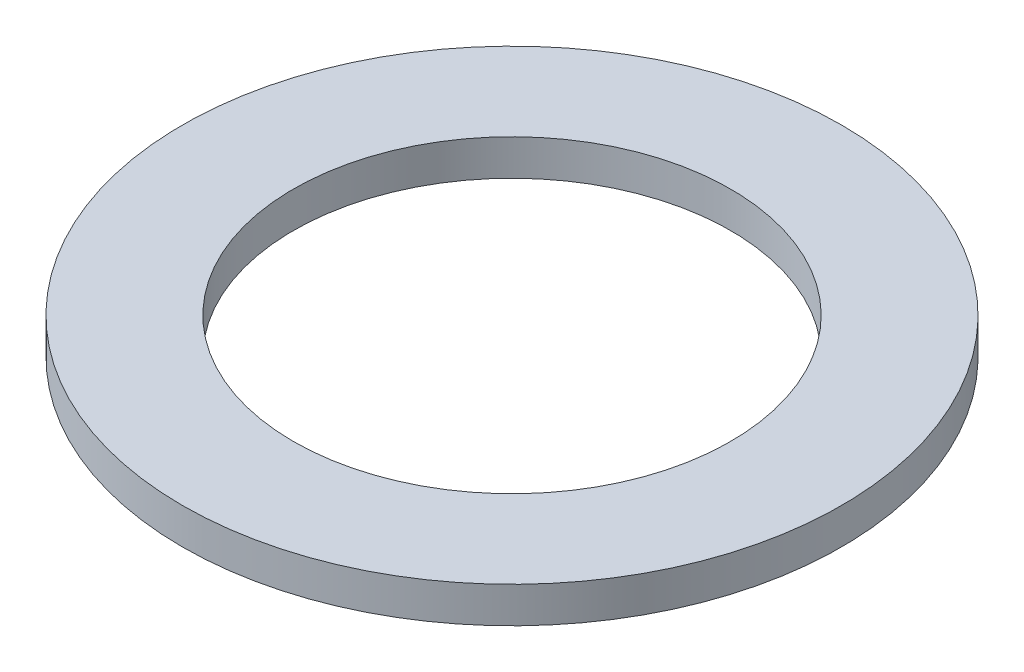
SolidWorks part; units mm, degrees
material "PET"
ref_plane "Front Plane" through (0, 0, 0) normal (0, 0, 1) x (1, 0, 0)
ref_plane "Top Plane" through (0, 0, 0) normal (0, 1, 0) x (1, 0, 0)
ref_plane "Right Plane" through (0, 0, 0) normal (1, 0, 0) x (0, 0, -1)
sketch "Sketch1" plane through (0, 0, 0) normal (0, 1, 0) x (1, 0, 0)
  circle A0 centre (0, 0) radius 7.2746
  circle A1 centre (0, 0) radius 4.826
  dimension "D1" = 9.652
  dimension "D2" = 14.5492
extrude "Boss-Extrude1" add sketch "Sketch1" along normal blind 0.7937
